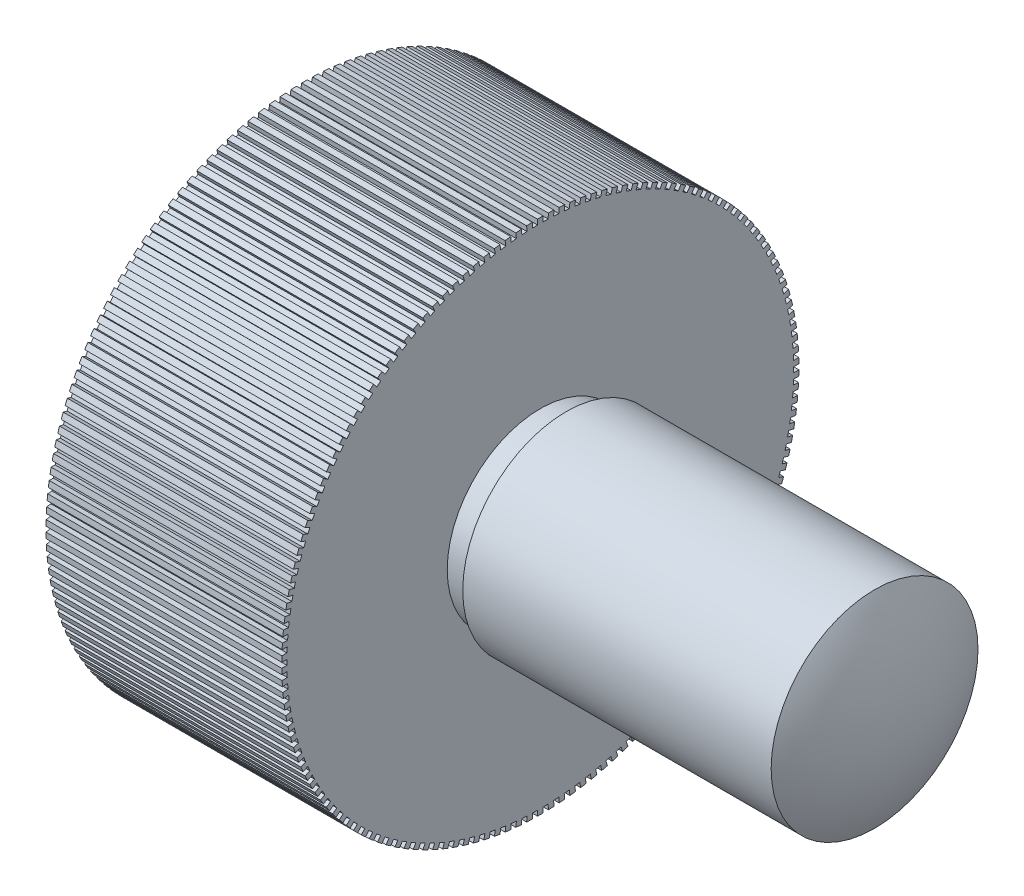
SolidWorks part; units mm, degrees
ref_plane "前视基准面" through (0, 0, 0) normal (0, 0, 1) x (1, 0, 0)
ref_plane "上视基准面" through (0, 0, 0) normal (0, 1, 0) x (1, 0, 0)
ref_plane "右视基准面" through (0, 0, 0) normal (1, 0, 0) x (0, 0, -1)
sketch "草图1" plane through (0, 0, 0) normal (0, 0, 1) x (1, 0, 0)
  line L1 (0, 0) -> (5, 0)
  line L2 (0, 0) -> (0, 5)
  line L3 (0, 5) -> (5, 5)
  line L4 (5, 0) -> (5, 5)
  line L5 (5, 0) -> (5.5, 0)
  line L6 (5, 0) -> (5, 1.8)
  line L7 (5, 1.8) -> (5.5, 1.8)
  line L8 (5.5, 0) -> (5.5, 1.8)
  line L9 (5.5, 0) -> (12, 0)
  line L10 (5.5, 0) -> (5.5, 2)
  line L11 (5.5, 2) -> (12, 2)
  line L12 (12, 0) -> (12, 2)
  circle A0 centre (8, 0) radius 4
  dimension "D7" = 8
  dimension "D1" = 5
  dimension "D2" = 5
  dimension "D3" = 12
  dimension "D4" = 0.5
  dimension "D5" = 2
  dimension "D6" = 0.2
revolve "旋转1" add sketch "草图1" angle 360 about L1 region at (2.3361, 2.6164, 0) region at (4.5954, 1.0111, 0) region at (5.25, 0.9, 0) region at (8.6652, 0.9861, 0)
cosmetic thread "装饰螺纹线1" parameters "D2"=3.22
sketch "草图2" plane through (0, 0, 0) normal (-1, 0, 0) x (0, 0, 1)
  circle A0 centre (0, 0) radius 2.5
extrude "切除-拉伸1" cut sketch "草图2" against normal through all draft 80 flip side to cut
sketch "草图3" plane through (5, 0, 0) normal (1, 0, 0) x (0, 0, -1)
  line L1 (-6.5957, 0.05) -> (6.5957, 0.05)
  line L2 (-6.5957, 0.05) -> (-6.5957, -0.05)
  line L3 (-6.5957, -0.05) -> (6.5957, -0.05)
  line L4 (6.5957, 0.05) -> (6.5957, -0.05)
  line L5 (-6.5957, 0.05) -> (6.5957, -0.05) construction
  line L6 (-6.5957, -0.05) -> (6.5957, 0.05) construction
  circle A0 centre (0, 0) radius 4.9
  circle A1 centre (0, 0) radius 5 construction
  circle M3 centre (0, 0) radius 5
  dimension "D2" = 0.1
  dimension "D1" = 0.1
extrude "切除-拉伸2" cut sketch "草图3" against normal through all contours L4 L1 L3 M3 | A0 L3 L1 M3 region at (5, 0, -4.9499) region at (5, 0, -5.7978)
pattern_circular "阵列(圆周)1" count 150 over 360 about axis through (0, 0, 0) along (-1, 0, 0) of "切除-拉伸2"
